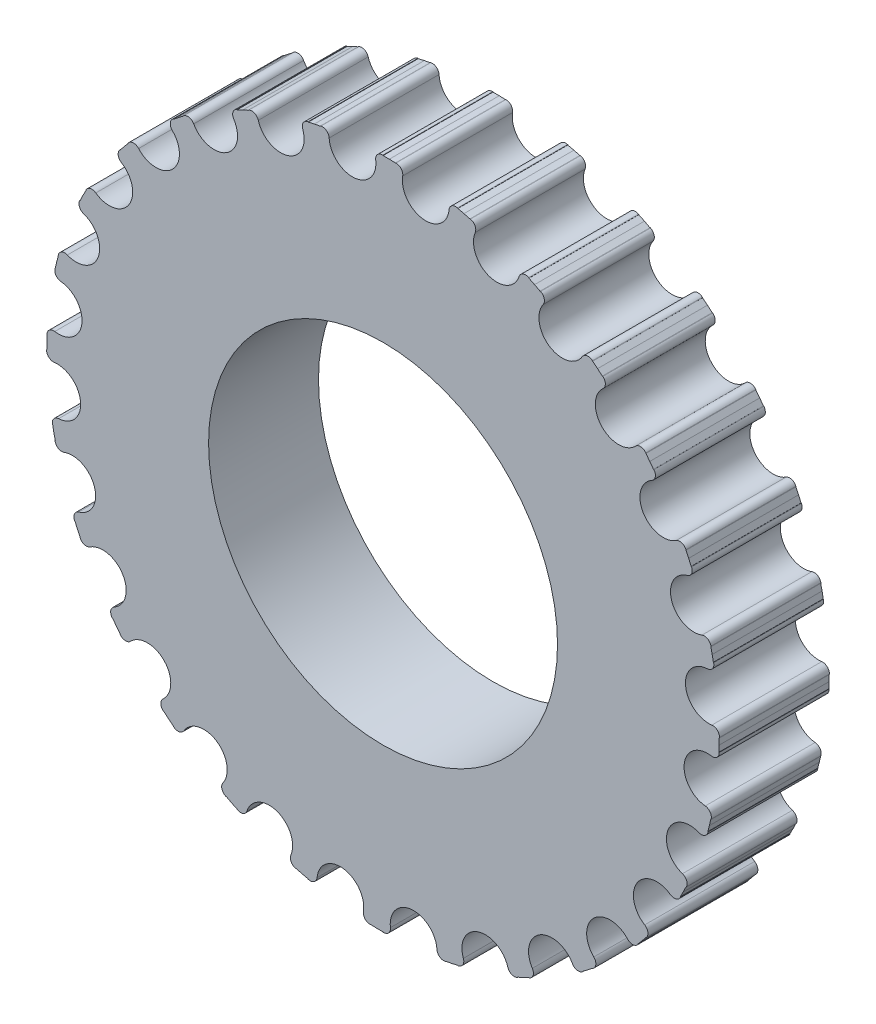
SolidWorks part; units mm, degrees
ref_plane "Front Plane" through (0, 0, 0) normal (0, 0, 1) x (1, 0, 0)
ref_plane "Top Plane" through (0, 0, 0) normal (0, 1, 0) x (1, 0, 0)
ref_plane "Right Plane" through (0, 0, 0) normal (1, 0, 0) x (0, 0, -1)
sketch "PD" plane through (0, 0, 0) normal (0, 0, 1) x (1, 0, 0)
  circle A0 centre (0, 0) radius 22.2817
  circle A1 centre (0, 0) radius 11.1125
  dimension "PD" = 44.5634
  dimension "D1" = 22.225
extrude "half width" add sketch "PD" along normal blind 7
sketch "Sketch3" plane through (0, 0, 7) normal (0, 0, 1) x (1, 0, 0)
  line L0 (0, 0) -> (0, 21.4117) construction
  line L1 (0, 21.4117) -> (0.827, 21.4117)
  line L2 (0, 0) -> (2.7204, 20.6634) construction
  line L3 (0, 21.4117) -> (0, 22.2817)
  line L4 (5.5418, 20.6821) -> (5.7669, 21.5225)
  line L5 (5.5418, 20.6821) -> (4.743, 20.8961)
  line L6 (2.7204, 20.6634) -> (2.9083, 22.0911) construction
  arc A0 (0.827, 21.4117) -> (1.251, 20.9104) centre (0.827, 20.9817) cw
  arc A1 (1.251, 20.9104) -> (4.2036, 20.5217) centre (2.7204, 20.6634) ccw
  circle A2 centre (0, 0) radius 22.2817 construction
  arc A3 (0, 22.2817) -> (5.7669, 21.5225) centre (0, 0) cw
  arc A4 (4.743, 20.8961) -> (4.2036, 20.5217) centre (4.6317, 20.4808) ccw
  point P8 (2.5259, 19.1861)
  dimension "D1" = 0.43
  dimension "D2" = 1.49
  dimension "D5" = 2.93
  dimension "D3" = 0.87
  dimension "D4" = 7.5
extrude "Teeth " cut sketch "Sketch3" against normal up to surface (7 mm away) up to face at (22.2817, 0, 0)
pattern_circular "CirPattern1" count 28 over 360 about axis through (0, 0, 7) along (0, 0, 1) of "Teeth "
equation "\"n\"= 28"
equation "\"p\"= 5'pitch"
equation "\"pd\"= \"n\" * \"p\" / pi'pitch diameter"
equation "\"PD@PD\"=\"pd\""
equation "\"D1@CirPattern1\"=\"n\""
equation "\"Bolt diameter\"= 3mm"
